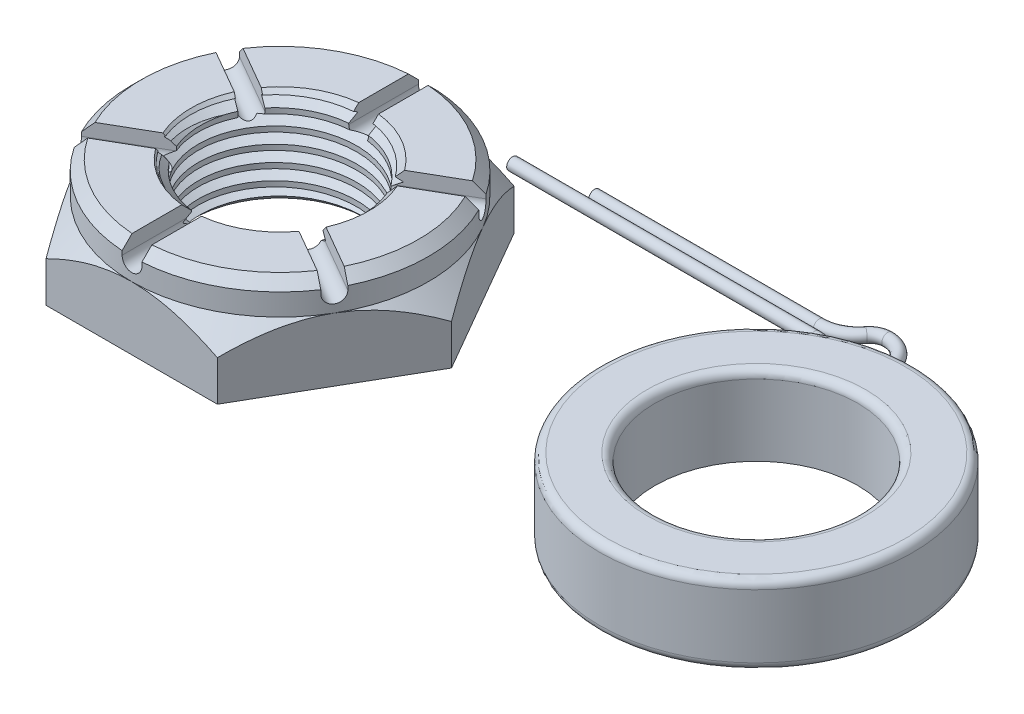
SolidWorks part; units mm, degrees
material "1060 Alloy"
ref_plane "Front Plane" through (0, 0, 0) normal (0, 0, 1) x (1, 0, 0)
ref_plane "Top Plane" through (0, 0, 0) normal (0, 1, 0) x (1, 0, 0)
ref_plane "Right Plane" through (0, 0, 0) normal (1, 0, 0) x (0, 0, -1)
sketch "Sketch1" plane through (0, 0, 0) normal (0, 1, 0) x (1, 0, 0)
  line L1 (21.6506, 0) -> (10.8253, 18.75)
  line L2 (10.8253, 18.75) -> (-10.8253, 18.75)
  line L3 (-10.8253, 18.75) -> (-21.6506, 0)
  line L4 (-21.6506, 0) -> (-10.8253, -18.75)
  line L5 (-10.8253, -18.75) -> (10.8253, -18.75)
  line L6 (10.8253, -18.75) -> (21.6506, 0)
  circle A0 centre (0, 0) radius 18.75 construction
  circle A1 centre (0, 0) radius 10
  dimension "D1" = 37.5
  dimension "D2" = 20
extrude "Boss-Extrude1" add sketch "Sketch1" along normal blind 8
sketch "Sketch2" plane through (0, 8, 0) normal (0, 1, 0) x (1, 0, 0)
  circle A0 centre (0, 0) radius 18.75
extrude "Cut-Extrude1" cut sketch "Sketch2" against normal blind 8 draft 45 flip side to cut
sketch "Sketch3" plane through (0, 8, 0) normal (0, 1, 0) x (1, 0, 0)
  circle A0 centre (0, 0) radius 18.75
  circle A1 centre (0, 0) radius 10
extrude "Boss-Extrude2" add sketch "Sketch3" along normal blind 4
chamfer "Chamfer1" distance 1.25 angle 45 1 edges at (0, 12, 18.75)
sketch "Sketch4" plane through (0, 0, 0) normal (0, 0, 1) x (1, 0, 0)
  line L1 (0, 8) -> (0, 13.2348) construction
  line L2 (-1.25, 10.25) -> (-1.25, 13.8633)
  line L3 (-1.25, 13.8633) -> (1.25, 13.8633)
  line L4 (1.25, 13.8633) -> (1.25, 10.25)
  line L6 (10, 12) -> (-10, 12) construction
  arc A0 (-1.25, 10.25) -> (1.25, 10.25) centre (0, 10.25) ccw
  point P11 (0, 9)
  dimension "D1" = 2.5
  dimension "D2" = 3
extrude "Cut-Extrude2" cut sketch "Sketch4" against normal through all
ref_axis "Axis1" through (0, 12, 0) along (0, -1, 0)
pattern_circular "CirPattern1" count 6 over 360 about axis through (0, 12, 0) along (0, -1, 0) of "Cut-Extrude2"
chamfer "Chamfer2" distance 1.25 angle 45 6 edges at (5, 12, 8.6603) (10, 12, 0) (5, 12, -8.6603) (-5, 12, 8.6603) (-10, 12, 0) (-5, 12, -8.6603)
chamfer "Chamfer3" distance 1 angle 45 1 edges at (0, 0, 10)
ref_plane "Plane1" through (0, -5, 0) normal (0, -1, 0) x (-1, 0, 0)
sketch "Sketch6" plane through (0, -5, 0) normal (0, -1, 0) x (-1, 0, 0)
  circle A1 centre (0, 0) radius 10 construction
  circle A2 centre (0, 0) radius 10
curve "Helix/Spiral2" pitch 2 height 22 radius 10 centre (0, -5, 0) axis (0, 1, 0) start towards (0, 0, -1)
sketch "Sketch7" plane through (0, 0, 0) normal (1, 0, 0) x (0, 0, -1)
  line L0 (-20.625, -5) -> (20.625, -5) construction
  line L5 (11.1489, -5) -> (9.4255, -4.005)
  line L6 (9.4255, -4.005) -> (9.4255, -5.995)
  line L7 (9.4255, -5.995) -> (11.1489, -5)
  circle A1 centre (10, -5) radius 0.5745 construction
  spline S0 degree 3 poles (10, -5) (10, -4.9586) (9.4793, -4.8749) (7.2552, -4.75) (3.9265, -4.625) (0, -4.5) (-3.9265, -4.375) (-7.2552, -4.25) (-9.4793, -4.125) (-10.2603, -4) (-9.4793, -3.875) (-7.2552, -3.75) (-3.9265, -3.625) (0, -3.5) (3.9265, -3.375) (7.2552, -3.25) (9.4793, -3.125) (10.2603, -3) (9.4793, -2.875) (7.2552, -2.75) (3.9265, -2.625) (0, -2.5) (-3.9265, -2.375) (-7.2552, -2.25) (-9.4793, -2.125) (-10.2603, -2) (-9.4793, -1.875) (-7.2552, -1.75) (-3.9265, -1.625) (0, -1.5) (3.9265, -1.375) (7.2552, -1.25) (9.4793, -1.125) (10.2603, -1) (9.4793, -0.875) (7.2552, -0.75) (3.9265, -0.625) (0, -0.5) (-3.9265, -0.375) (-7.2552, -0.25) (-9.4793, -0.125) (-10.2603, 0) (-9.4793, 0.125) (-7.2552, 0.25) (-3.9265, 0.375) (0, 0.5) (3.9265, 0.625) (7.2552, 0.75) (9.4793, 0.875) (10.2603, 1) (9.4793, 1.125) (7.2552, 1.25) (3.9265, 1.375) (0, 1.5) (-3.9265, 1.625) (-7.2552, 1.75) (-9.4793, 1.875) (-10.2603, 2) (-9.4793, 2.125) (-7.2552, 2.25) (-3.9265, 2.375) (0, 2.5) (3.9265, 2.625) (7.2552, 2.75) (9.4793, 2.875) (10.2603, 3) (9.4793, 3.125) (7.2552, 3.25) (3.9265, 3.375) (0, 3.5) (-3.9265, 3.625) (-7.2552, 3.75) (-9.4793, 3.875) (-10.2603, 4) (-9.4793, 4.125) (-7.2552, 4.25) (-3.9265, 4.375) (0, 4.5) (3.9265, 4.625) (7.2552, 4.75) (9.4793, 4.875) (10.2603, 5) (9.4793, 5.125) (7.2552, 5.25) (3.9265, 5.375) (0, 5.5) (-3.9265, 5.625) (-7.2552, 5.75) (-9.4793, 5.875) (-10.2603, 6) (-9.4793, 6.125) (-7.2552, 6.25) (-3.9265, 6.375) (0, 6.5) (3.9265, 6.625) (7.2552, 6.75) (9.4793, 6.875) (10.2603, 7) (9.4793, 7.125) (7.2552, 7.25) (3.9265, 7.375) (0, 7.5) (-3.9265, 7.625) (-7.2552, 7.75) (-9.4793, 7.875) (-10.2603, 8) (-9.4793, 8.125) (-7.2552, 8.25) (-3.9265, 8.375) (0, 8.5) (3.9265, 8.625) (7.2552, 8.75) (9.4793, 8.875) (10.2603, 9) (9.4793, 9.125) (7.2552, 9.25) (3.9265, 9.375) (0, 9.5) (-3.9265, 9.625) (-7.2552, 9.75) (-9.4793, 9.875) (-10.2603, 10) (-9.4793, 10.125) (-7.2552, 10.25) (-3.9265, 10.375) (0, 10.5) (3.9265, 10.625) (7.2552, 10.75) (9.4793, 10.875) (10.2603, 11) (9.4793, 11.125) (7.2552, 11.25) (3.9265, 11.375) (0, 11.5) (-3.9265, 11.625) (-7.2552, 11.75) (-9.4793, 11.875) (-10.2603, 12) (-9.4793, 12.125) (-7.2552, 12.25) (-3.9265, 12.375) (0, 12.5) (3.9265, 12.625) (7.2552, 12.75) (9.4793, 12.875) (10.2603, 13) (9.4793, 13.125) (7.2552, 13.25) (3.9265, 13.375) (0, 13.5) (-3.9265, 13.625) (-7.2552, 13.75) (-9.4793, 13.875) (-10.2603, 14) (-9.4793, 14.125) (-7.2552, 14.25) (-3.9265, 14.375) (0, 14.5) (3.9265, 14.625) (7.2552, 14.75) (9.4793, 14.875) (10.2603, 15) (9.4793, 15.125) (7.2552, 15.25) (3.9265, 15.375) (0, 15.5) (-3.9265, 15.625) (-7.2552, 15.75) (-9.4793, 15.875) (-10.2603, 16) (-9.4793, 16.125) (-7.2552, 16.25) (-3.9265, 16.375) (0, 16.5) (3.9265, 16.625) (7.2552, 16.75) (9.4793, 16.8749) (10, 16.9586) (10, 17) knots 0 0 0 0 0.005682 0.011364 0.017045 0.022727 0.028409 0.034091 0.039773 0.045455 0.051136 0.056818 0.0625 0.068182 0.073864 0.079545 0.085227 0.090909 0.096591 0.102273 0.107955 0.113636 0.119318 0.125 0.130682 0.136364 0.142045 0.147727 0.153409 0.159091 0.164773 0.170455 0.176136 0.181818 0.1875 0.193182 0.198864 0.204545 0.210227 0.215909 0.221591 0.227273 0.232955 0.238636 0.244318 0.25 0.255682 0.261364 0.267045 0.272727 0.278409 0.284091 0.289773 0.295455 0.301136 0.306818 0.3125 0.318182 0.323864 0.329545 0.335227 0.340909 0.346591 0.352273 0.357955 0.363636 0.369318 0.375 0.380682 0.386364 0.392045 0.397727 0.403409 0.409091 0.414773 0.420455 0.426136 0.431818 0.4375 0.443182 0.448864 0.454545 0.460227 0.465909 0.471591 0.477273 0.482955 0.488636 0.494318 0.5 0.505682 0.511364 0.517045 0.522727 0.528409 0.534091 0.539773 0.545455 0.551136 0.556818 0.5625 0.568182 0.573864 0.579545 0.585227 0.590909 0.596591 0.602273 0.607955 0.613636 0.619318 0.625 0.630682 0.636364 0.642045 0.647727 0.653409 0.659091 0.664773 0.670455 0.676136 0.681818 0.6875 0.693182 0.698864 0.704545 0.710227 0.715909 0.721591 0.727273 0.732955 0.738636 0.744318 0.75 0.755682 0.761364 0.767045 0.772727 0.778409 0.784091 0.789773 0.795455 0.801136 0.806818 0.8125 0.818182 0.823864 0.829545 0.835227 0.840909 0.846591 0.852273 0.857955 0.863636 0.869318 0.875 0.880682 0.886364 0.892045 0.897727 0.903409 0.909091 0.914773 0.920455 0.926136 0.931818 0.9375 0.943182 0.948864 0.954545 0.960227 0.965909 0.971591 0.977273 0.982955 0.988636 0.994318 1 1 1 1 construction
  dimension "D1" = 1.99
sweep "Cut-Sweep1" cut profiles "Sketch7" path "Helix/Spiral2" align with end faces yes
sketch "Sketch8" plane through (0, 0, 0) normal (0, 1, 0) x (1, 0, 0)
  circle A0 centre (60.1682, 0) radius 19.8117
extrude "Extrude-Thin1" add sketch "Sketch8" along normal blind 10 separate body thin thin type one direction reverse wall 7
sketch "Sketch9" plane through (0, 0, 0) normal (0, 1, 0) x (1, 0, 0)
  line L0 (3.1332, 26.2402) -> (41.3052, 26.2402)
  line L1 (40.2607, 27.8402) -> (11.8766, 27.8402)
  arc A0 (44.7683, 24.8467) -> (46.1333, 24.3085) centre (46.1064, 26.2402) ccw
  arc A1 (46.1333, 24.3085) -> (46.0441, 30.7092) centre (46.0887, 27.5088) ccw
  arc A2 (46.0441, 30.7092) -> (44.2284, 29.7976) centre (46.0765, 28.3805) ccw
  arc A3 (44.2284, 29.7976) -> (40.2607, 27.8402) centre (40.2607, 32.8402) cw
  arc A4 (41.3052, 26.2402) -> (44.7683, 24.8467) centre (41.3052, 21.2402) cw
  point P13 (3.1332, 26.2402)
  point P14 (11.8766, 27.6263)
  dimension "D1" = 5
  dimension "D2" = 1.6
ref_plane "Plane2" through (3.1332, 0, -26.2402) normal (1, 0, 0) x (0, 0, -1)
sketch "Sketch10" plane through (3.1332, 0, -26.2402) normal (1, 0, 0) x (0, 0, -1)
  line L0 (0, 0) -> (-1.3935, 0) construction
  line L1 (4.4693, 0) -> (-1.9317, 0) construction
  circle A0 centre (0, 0) radius 0.75
  dimension "D1" = 1.5
sweep "Sweep1" add profiles "Sketch10" path "Sketch9"
fillet "Fillet1" radius 1 3 edges at (60.1682, 0, 19.8117) (72.9798, 10, 0) (60.1682, 10, 19.8117)
